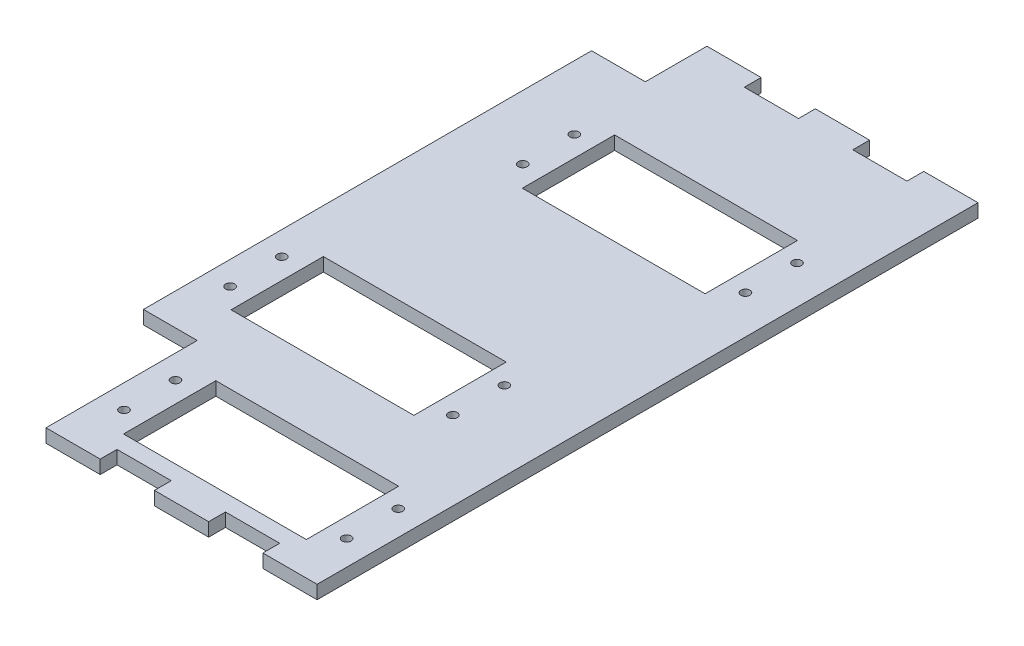
SolidWorks part; units mm, degrees
material "ABS"
ref_plane "Front Plane" through (0, 0, 0) normal (0, 0, 1) x (1, 0, 0)
ref_plane "Top Plane" through (0, 0, 0) normal (0, 1, 0) x (1, 0, 0)
ref_plane "Right Plane" through (0, 0, 0) normal (1, 0, 0) x (0, 0, -1)
sketch "Sketch1" plane through (0, 0, 0) normal (0, 1, 0) x (1, 0, 0)
  line L0 (0, -70) -> (0, -56) construction
  line L1 (-30.25, -70) -> (30.25, -70) construction
  line L2 (-30.25, -70) -> (-30.25, 70) construction
  line L4 (30.25, -70) -> (30.25, 70)
  line L5 (-30.25, -70) -> (30.25, 70) construction
  line L6 (-30.25, 70) -> (30.25, -70) construction
  line L7 (0, -56) -> (0, -20) construction
  line L8 (-20.4, -45.7) -> (20.4, -45.7)
  line L9 (-20.4, -45.7) -> (-20.4, -66.3)
  line L10 (-20.4, -66.3) -> (20.4, -66.3)
  line L11 (20.4, -45.7) -> (20.4, -66.3)
  line L12 (-20.4, -45.7) -> (20.4, -66.3) construction
  line L13 (-20.4, -66.3) -> (20.4, -45.7) construction
  line L14 (0, -20) -> (0, 36) construction
  line L15 (-20.4, -9.7) -> (20.4, -9.7) construction
  line L16 (-20.4, -9.7) -> (-20.4, -30.3) construction
  line L17 (-20.4, -30.3) -> (20.4, -30.3) construction
  line L18 (20.4, -9.7) -> (20.4, -30.3) construction
  line L19 (-20.4, -9.7) -> (20.4, -30.3) construction
  line L20 (-20.4, -30.3) -> (20.4, -9.7) construction
  line L21 (-30.25, -70) -> (30.25, -70) construction
  line L22 (-20.4, 25.7) -> (20.4, 25.7) construction
  line L23 (-20.4, 25.7) -> (-20.4, 46.3) construction
  line L24 (-20.4, 46.3) -> (20.4, 46.3) construction
  line L25 (20.4, 25.7) -> (20.4, 46.3) construction
  line L26 (-20.4, 25.7) -> (20.4, 46.3) construction
  line L27 (-20.4, 46.3) -> (20.4, 25.7) construction
  line L28 (-30.25, -70) -> (-30.25, -73.75)
  line L29 (30.25, -70) -> (30.25, -73.75)
  line L31 (30.25, -71.875) -> (18.15, -71.875) construction
  line L32 (18.15, -70) -> (18.15, -73.75)
  line L33 (30.25, -73.75) -> (18.15, -73.75)
  line L34 (30.25, -73.75) -> (30.25, -70)
  line L35 (6.05, -70) -> (18.15, -70)
  line L36 (18.15, -73.75) -> (6.05, -73.75) construction
  line L37 (6.05, -73.75) -> (6.05, -70)
  line L38 (6.05, -73.75) -> (-6.05, -73.75)
  line L39 (-6.05, -73.75) -> (-18.15, -73.75) construction
  line L40 (-18.15, -73.75) -> (-30.25, -73.75)
  line L41 (-6.05, -73.75) -> (-6.05, -70)
  line L42 (-18.15, -73.75) -> (-18.15, -70)
  line L43 (-6.05, -70) -> (-18.15, -70)
  line L44 (30.25, 0) -> (-30.25, 0) construction
  line L45 (-6.05, 70) -> (-18.15, 70)
  line L46 (6.05, 70) -> (18.15, 70)
  line L47 (-18.15, 73.75) -> (-30.25, 73.75)
  line L48 (-6.05, 73.75) -> (-18.15, 73.75) construction
  line L49 (18.15, 73.75) -> (6.05, 73.75) construction
  line L50 (30.25, 71.875) -> (18.15, 71.875) construction
  line L51 (-18.15, 73.75) -> (-18.15, 70)
  line L52 (-6.05, 73.75) -> (-6.05, 70)
  line L53 (6.05, 73.75) -> (-6.05, 73.75)
  line L54 (6.05, 73.75) -> (6.05, 70)
  line L55 (30.25, 73.75) -> (30.25, 70)
  line L56 (30.25, 73.75) -> (18.15, 73.75)
  line L57 (18.15, 70) -> (18.15, 73.75)
  line L58 (30.25, 70) -> (30.25, 73.75)
  line L59 (-30.25, 70) -> (-30.25, 73.75)
  line L60 (-30.25, -70) -> (-30.25, -40)
  line L61 (-30.25, -40) -> (-42.25, -40)
  line L62 (-42.25, -40) -> (-42.25, 60)
  line L63 (-42.25, 60) -> (-30.25, 60)
  line L64 (-30.25, 60) -> (-30.25, 70)
  line L65 (0, -20) -> (-12, -20) construction
  line L66 (0, 36) -> (-3, 36) construction
  line L67 (8.4, -9.7) -> (-32.4, -9.7)
  line L68 (8.4, -9.7) -> (8.4, -30.3)
  line L69 (8.4, -30.3) -> (-32.4, -30.3)
  line L70 (-32.4, -9.7) -> (-32.4, -30.3)
  line L71 (8.4, -9.7) -> (-32.4, -30.3) construction
  line L72 (8.4, -30.3) -> (-32.4, -9.7) construction
  line L74 (17.4, 46.3) -> (-23.4, 46.3)
  line L75 (17.4, 46.3) -> (17.4, 25.7)
  line L76 (17.4, 25.7) -> (-23.4, 25.7)
  line L77 (-23.4, 46.3) -> (-23.4, 25.7)
  line L78 (17.4, 46.3) -> (-23.4, 25.7) construction
  line L79 (17.4, 25.7) -> (-23.4, 46.3) construction
  circle A0 centre (-25.6879, -6.6503) radius 1.8167 construction
  point P0 (0, 0)
  point P29 (18.15, -71.875)
  dimension "D1" = 140
  dimension "D2" = 60.5
  dimension "D3" = 14
  dimension "D4" = 40.8
  dimension "D5" = 20.6
  dimension "D6" = 36
  dimension "D7" = 20.6
  dimension "D8" = 40.8
  dimension "D9" = 56
  dimension "D10" = 20.6
  dimension "D11" = 40.8
  dimension "D12" = 3.75
  dimension "D13" = 12.1
  dimension "D14" = 12.1
  dimension "D15" = 12.1
  dimension "D16" = 12.1
  dimension "D17" = 12
  dimension "D18" = 100
  dimension "D19" = 30
  dimension "D20" = 12
  dimension "D21" = 40.8
  dimension "D22" = 20.6
  dimension "D23" = 3
  dimension "D24" = 20.6
  dimension "D25" = 40.8
extrude "Boss-Extrude4" add sketch "Sketch1" along normal blind 3 contours L2 L21 L4 L25 L22 L23 L24 L15 L18 L17 L16 L8 L11 L10 L9 | L28 L29 L21 region at (-4.163, 0, -6.1475)
sketch "Sketch2" plane through (0, 3, 0) normal (0, 1, 0) x (1, 0, 0)
  line L0 (30.25, 73.75) -> (30.25, -73.75) construction
  circle A0 centre (-25, -50.1) radius 1
  circle A1 centre (-25, -61.6) radius 1
  circle A2 centre (-37, -25.9) radius 1
  circle A3 centre (-28, 30.4) radius 1
  circle A4 centre (-28, 41.9) radius 1
  circle A5 centre (21.7, 41.9) radius 1
  circle A6 centre (21.7, 30.4) radius 1
  circle A7 centre (12.7, -14.4) radius 1
  circle A8 centre (12.7, -25.9) radius 1
  circle A9 centre (24.7, -50.1) radius 1
  circle A10 centre (24.7, -61.6) radius 1
  circle A11 centre (-37, -14.4) radius 1
  dimension "D1" = 2
  dimension "D2" = 2
  dimension "D3" = 2
  dimension "D4" = 2
  dimension "D5" = 2
  dimension "D6" = 2
  dimension "D7" = 2
  dimension "D8" = 2
  dimension "D9" = 2
  dimension "D10" = 2
  dimension "D11" = 2
  dimension "D12" = 2
  dimension "D13" = 17.55
  dimension "D14" = 17.55
  dimension "D15" = 67.25
  dimension "D16" = 67.25
  dimension "D17" = 5.55
  dimension "D18" = 5.55
  dimension "D19" = 55.25
  dimension "D20" = 55.25
  dimension "D21" = 8.55
  dimension "D22" = 8.55
  dimension "D23" = 58.25
  dimension "D24" = 58.25
extrude "Cut-Extrude1" cut sketch "Sketch2" against normal through all
equation "\"MotorLength\" = 40.5mm"
equation "\"MotorWidth\" = 20.3mm"
equation "\"AttachmentHeight\"= 3mm"
equation "\"SpoolDiameter\"= 60mm"
equation "\"SpoolHeight\"= 2mm"
equation "\"SpoolRidgeHeight\"= 1mm"
equation "\"SpoolRidgeDepth\"= 2mm"
equation "\"OuterThickness\"= 3mm"
equation "\"MasterFillet\"= 3mm"
equation "\"PartSeperation\"= 6mm"
equation "\"Tolerance\"= 0.15mm"
equation "\"HeightPart\"= 100mm"
equation "\"Holes\"= 1.5mm"
equation "\"SpineHolderThickness\"= 3mm"
equation "\"SpineHolderDepth\" = 3mm"
equation "\"SpoolSeperation\"= 2mm"
equation "\"D1@Sketch1\"=3*((\"SpoolDiameter\"/3)*2+\"SpoolRidgeDepth\"*2+\"SpoolSeperation\")+\"SpoolSeperation\""
equation "\"D2@Sketch1\"=\"MotorLength\"+\"ServoHolderWidthOffset\""
equation "\"D3@Sketch1\"=\"SpoolSeperation\"+( \"SpoolRidgeDepth\")+\"SpoolDiameter\"/(2*3)"
equation "\"D4@Sketch1\"=\"MotorLength\"+\"Tolerance\"*2"
equation "\"D5@Sketch1\"=\"MotorWidth\"+\"Tolerance\"*2"
equation "\"D6@Sketch1\"=(\"SpoolDiameter\")/(3*2)+(\"SpoolDiameter\"/3)+\"SpoolSeperation\"+\"SpoolRidgeDepth\"*2"
equation "\"D7@Sketch1\"=\"MotorWidth\"+\"Tolerance\"*2"
equation "\"D8@Sketch1\"=\"MotorLength\"+\"Tolerance\"*2"
equation "\"D9@Sketch1\"=\"SpoolDiameter\"/2+\"SpoolDiameter\"/3+\"SpoolSeperation\"+\"SpoolRidgeDepth\"*2"
equation "\"D10@Sketch1\"=\"MotorWidth\"+\"Tolerance\"*2"
equation "\"D11@Sketch1\"=\"MotorLength\"+\"Tolerance\"*2"
equation "\"D12@Sketch1\"=\"SpineHolderDepth\"*1.25"
equation "\"D13@Sketch1\"=(\"MotorLength\"+\"ServoHolderWidthOffset\")*1/5"
equation "\"D14@Sketch1\"=(\"MotorLength\"+\"ServoHolderWidthOffset\")*1/5"
equation "\"D15@Sketch1\"=(\"MotorLength\"+\"ServoHolderWidthOffset\")*1/5"
equation "\"D16@Sketch1\"=(\"MotorLength\"+\"ServoHolderWidthOffset\")*1/5"
equation "\"ServoHolderWidthOffset\"= 20mm"
equation "\"ServoFastenerHolders\"=2mm"
equation "\"D1@Sketch2\"=\"ServoFastenerHolders\""
equation "\"D2@Sketch2\"=\"ServoFastenerHolders\""
equation "\"D3@Sketch2\"=\"ServoFastenerHolders\""
equation "\"D4@Sketch2\"=\"ServoFastenerHolders\""
equation "\"D5@Sketch2\"=\"ServoFastenerHolders\""
equation "\"D6@Sketch2\"=\"ServoFastenerHolders\""
equation "\"D7@Sketch2\"=\"ServoFastenerHolders\""
equation "\"D8@Sketch2\"=\"ServoFastenerHolders\""
equation "\"D9@Sketch2\"=\"ServoFastenerHolders\""
equation "\"D11@Sketch2\"=\"ServoFastenerHolders\""
equation "\"D12@Sketch2\"=\"ServoFastenerHolders\""
equation "\"MotorTransmitterToScrew\"= 21.7mm"
equation "\"SpoolToSpine\"= 15mm"
equation "\"SpoolCenterToMotor\" = 31.5mm"
equation "\"HubOffset\"= 18mm"
equation "\"MiddleServoOffset\"= 12mm"
equation "\"LargeServoOffset\"= 3mm"
equation "\"SmallServoOffset\"= 0mm"
equation "\"D20@Sketch1\"=\"MiddleServoOffset\""
equation "\"D13@Sketch2\"=\"MiddleServoOffset\"+5.55"
equation "\"D14@Sketch2\"=\"MiddleServoOffset\"+5.55"
equation "\"D15@Sketch2\"=\"MiddleServoOffset\"+55.25"
equation "\"D16@Sketch2\"=\"MiddleServoOffset\"+55.25"
equation "\"D17@Sketch2\"=\"SmallServoOffset\"+5.55"
equation "\"D18@Sketch2\"=\"SmallServoOffset\"+5.55"
equation "\"D19@Sketch2\"=\"SmallServoOffset\"+55.25"
equation "\"D20@Sketch2\"=\"SmallServoOffset\"+55.25"
equation "\"D21@Sketch2\"=\"LargeServoOffset\"+5.55"
equation "\"D22@Sketch2\"=\"LargeServoOffset\"+5.55"
equation "\"D23@Sketch2\"=\"LargeServoOffset\"+55.25"
equation "\"D24@Sketch2\"=\"LargeServoOffset\"+55.25"
equation "\"D23@Sketch1\"=\"LargeServoOffset\""
equation "\"D24@Sketch1\"=\"MotorWidth\"+\"Tolerance\"*2"
equation "\"D25@Sketch1\"=\"MotorLength\"+\"Tolerance\"*2"
equation "\"D17@Sketch1\"=\"MiddleServoOffset\""
equation "\"D10@Sketch2\"=\"ServoFastenerHolders\""
equation "\"DiscThickness\"= 4mm"
equation "\"LigamentThickness\"= 2mm"
equation "\"LigamentExtension\"= 1mm"
equation "\"LigamentAngle\"= 20deg"
equation "\"SpineDiameter\"= 15mm"
equation "\"LigamentDepth\"= 1mm"
equation "\"ArduinoLength\" = 53.4mm"
equation "\"ArduinoWidth\" = 50mm"
equation "\"ArdYOffset\" = 29.5mm"
equation "\"ArdXOffset\" = 20.5mm"
equation "\"ArdXOffsetSmall\" = 25mm"
equation "\"ToolHoleDiameter\"= 12mm"
